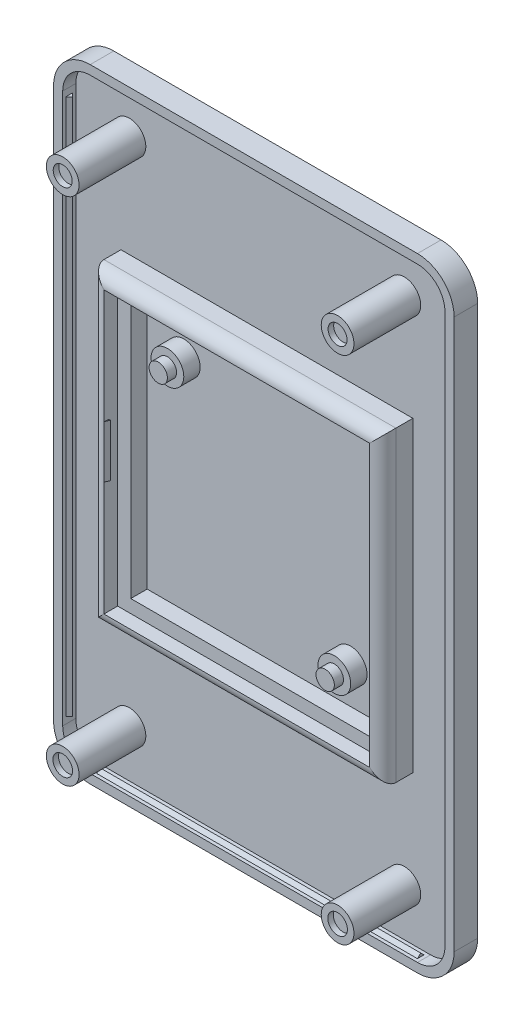
SolidWorks part; units mm, degrees
ref_plane "Front Plane" through (0, 0, 0) normal (0, 0, 1) x (1, 0, 0)
ref_plane "Top Plane" through (0, 0, 0) normal (0, 1, 0) x (1, 0, 0)
ref_plane "Right Plane" through (0, 0, 0) normal (1, 0, 0) x (0, 0, -1)
sketch "Esquisse2" plane through (0, 0, 0) normal (0, 0, 1) x (1, 0, 0)
  line L1 (-29.2, -46.2) -> (29.2, -46.2)
  line L2 (-29.2, -46.2) -> (-29.2, 46.2)
  line L3 (-29.2, 46.2) -> (29.2, 46.2)
  line L4 (29.2, -46.2) -> (29.2, 46.2)
  line L5 (-29.2, -46.2) -> (29.2, 46.2) construction
  line L6 (-29.2, 46.2) -> (29.2, -46.2) construction
  point P0 (0, 0)
  dimension "D1" = 92.4
  dimension "D2" = 58.4
extrude "Boss.-Extru.1" add sketch "Esquisse2" against normal blind 1.6
fillet "Congé1" radius 4.2 4 edges at (-29.2, 46.2, -0.8) (29.2, 46.2, -0.8) (29.2, -46.2, -0.8) (-29.2, -46.2, -0.8)
sketch "Esquisse3" plane through (0, 0, 0) normal (0, 0, 1) x (1, 0, 0)
  line L1 (20.3, -21.45) -> (-20.3, -21.45)
  line L2 (20.3, -21.45) -> (20.3, 21.45)
  line L3 (20.3, 21.45) -> (-20.3, 21.45)
  line L4 (-20.3, -21.45) -> (-20.3, 21.45)
  line L5 (20.3, -21.45) -> (-20.3, 21.45) construction
  line L6 (20.3, 21.45) -> (-20.3, -21.45) construction
  point P0 (0, 0)
  dimension "D1" = 42.9
  dimension "D2" = 40.6
extrude "Extru.-Mince1" add sketch "Esquisse3" along normal blind 2.5 thin contours L4 L3 L2 L1 thin type one direction reverse wall 2
sketch "Esquisse4" plane through (0, 0, 0) normal (0, 0, 1) x (1, 0, 0)
  line L0 (20.3, 21.45) -> (-20.3, 21.45) construction
  line L1 (-12.7, 13.95) -> (-20.2, 13.95)
  line L2 (-12.7, 13.95) -> (-12.7, 21.45)
  line L3 (-12.7, 21.45) -> (-20.2, 21.45)
  line L4 (-20.2, 13.95) -> (-20.2, 21.45)
  line L5 (-12.7, 13.95) -> (-20.2, 21.45) construction
  line L6 (-12.7, 21.45) -> (-20.2, 13.95) construction
  circle A0 centre (-12.7, 13.95) radius 2.5
  point P0 (-16.45, 17.7)
  dimension "D1" = 7.5
  dimension "D2" = 7.5
extrude "Boss.-Extru.2" add sketch "Esquisse4" along normal blind 2.5 contours A0
sketch "Esquisse5" plane through (0, 0, 0) normal (0, 0, 1) x (1, 0, 0)
  circle A0 centre (-12.7, 13.95) radius 1.4
extrude "Boss.-Extru.3" add sketch "Esquisse5" along normal blind 3.9
sketch "Esquisse6" plane through (0, 0, 0) normal (0, 0, 1) x (1, 0, 0)
  line L1 (20.3, -21.45) -> (12.8, -21.45) construction
  line L2 (20.3, -21.45) -> (20.3, -13.95) construction
  line L3 (20.3, -13.95) -> (12.8, -13.95) construction
  line L4 (12.8, -21.45) -> (12.8, -13.95)
  circle A0 centre (12.8, -13.95) radius 2.5
  dimension "D1" = 7.5
  dimension "D2" = 7.5
extrude "Boss.-Extru.4" add sketch "Esquisse6" along normal blind 2.5 contours A0
sketch "Esquisse7" plane through (0, 0, 0) normal (0, 0, 1) x (1, 0, 0)
  circle A0 centre (12.8, -13.95) radius 1.4
extrude "Boss.-Extru.5" add sketch "Esquisse7" along normal blind 3.9 contours A0
sketch "Esquisse8" plane through (0, 0, 0) normal (0, 0, 1) x (1, 0, 0)
  line L1 (20.3, -21.45) -> (-20.3, -21.45)
  line L2 (20.3, -21.45) -> (20.3, 21.45)
  line L3 (20.3, 21.45) -> (-20.3, 21.45)
  line L4 (-20.3, -21.45) -> (-20.3, 21.45)
extrude "Extru.-Mince2" add sketch "Esquisse8" along normal blind 4.6 thin thin type one direction wall 2
fillet "Congé2" radius 2 4 edges at (22.3, 0, 4.6) (0, 23.45, 4.6) (-22.3, 0, 4.6) (0, -23.45, 4.6)
sketch "Esquisse10" plane through (0, 0, 0) normal (0, 0, 1) x (1, 0, 0)
  line L1 (21, -39) -> (-21, -39)
  line L2 (21, -39) -> (21, 39)
  line L3 (21, 39) -> (-21, 39)
  line L4 (-21, -39) -> (-21, 39)
  line L5 (21, -39) -> (-21, 39) construction
  line L6 (21, 39) -> (-21, -39) construction
  circle A0 centre (21, -39) radius 2.5
  circle A1 centre (-21, -39) radius 2.5
  circle A2 centre (-21, 39) radius 2.5
  circle A3 centre (21, 39) radius 2.5
  point P0 (0, 0)
  dimension "D1" = 78
  dimension "D2" = 42
extrude "Boss.-Extru.6" add sketch "Esquisse10" along normal blind 10.2 contours A1 | A0 | A3 | A2
sketch "Esquisse13" plane through (0, 0, 10.2) normal (0, 0, 1) x (1, 0, 0)
  circle A0 centre (21, -39) radius 1.5
  circle A1 centre (-21, -39) radius 1.5
  circle A2 centre (-21, 39) radius 1.45
  circle A3 centre (21, 39) radius 1.45
extrude "Enlèv. mat.-Extru.1" cut sketch "Esquisse13" against normal blind 0.85
sketch "Esquisse14" plane through (0, 0, 0) normal (0, 0, 1) x (1, 0, 0)
  line L0 (25, 46.2) -> (-25, 46.2) construction
  line L1 (29.2, -42) -> (29.2, 42) construction
  line L2 (-29.2, 42) -> (-29.2, -42) construction
  line L3 (-25, -46.2) -> (25, -46.2) construction
  line L4 (25, 46.2) -> (-25, 46.2)
  line L5 (29.2, -42) -> (29.2, 42)
  line L6 (-29.2, 42) -> (-29.2, -42)
  line L7 (-25, -46.2) -> (25, -46.2)
  arc A0 (-25, 46.2) -> (-29.2, 42) centre (-25, 42) ccw construction
  arc A1 (29.2, 42) -> (25, 46.2) centre (25, 42) ccw construction
  arc A2 (25, -46.2) -> (29.2, -42) centre (25, -42) ccw construction
  arc A3 (-29.2, -42) -> (-25, -46.2) centre (-25, -42) ccw construction
  arc A4 (-25, 46.2) -> (-29.2, 42) centre (-25, 42) ccw
  arc A5 (29.2, 42) -> (25, 46.2) centre (25, 42) ccw
  arc A6 (25, -46.2) -> (29.2, -42) centre (25, -42) ccw
  arc A7 (-29.2, -42) -> (-25, -46.2) centre (-25, -42) ccw
extrude "Extru.-Mince3" add sketch "Esquisse14" along normal blind 2 and the other way blind 1.6 thin thin type one direction wall 1.4
sketch3d "Esquisse3D7"
  line L0 (20.3, -21.45, 4.6) -> (20.3, 0, 4.6) construction
  line L1 (20.3, -21.45, 4.6) -> (20.3, 21.45, 4.6) construction
  line L2 (20.3, 0, 4.6) -> (20.3, 0, 3.9)
  line L3 (20.3, 0, 4.6) -> (20.05, 0, 3.9)
  line L4 (20.05, 0, 3.9) -> (20.3, 0, 3.9)
extrude "Boss.-Extru.9" add sketch "Esquisse3D7" along direction (0, 1, 0) on the side of the normal blind 4 and the other way blind 4 contours L3 L4 L2
sketch3d "Esquisse3D8"
  line L0 (-20.3, 0, 4.6) -> (-20.0062, 0, 3.9153)
  line L1 (-20.3, 21.45, 4.6) -> (-20.3, -21.45, 4.6) construction
  line L2 (-20.0062, 0, 3.9153) -> (-20.2371, 0, 3.8947)
  line L3 (-20.2371, 0, 3.8947) -> (-20.3, 0, 4.6)
extrude "Boss.-Extru.10" add sketch "Esquisse3D8" along direction (0, -1, 0) on the side of the normal blind 4 and the other way blind 4 separate body
sketch "Esquisse16" plane through (29.2, 0, 0) normal (-1, 0, 0) x (0, 0, 1)
  line L0 (2, 0) -> (0, 0)
  line L1 (2, -42) -> (2, 42) construction
  line L2 (0, -42) -> (0, 42) construction
sketch3d "Esquisse3D9"
  line L2 (29.2, 0, 1) -> (29.2, 0, 1.5111)
  line L3 (29.2, 0, 2) -> (29.2, 0, 0) construction
  line L4 (29.2, 0, 1) -> (29.2, 0, 0.4889)
  line L6 (20.3, -21.45, 4.6) -> (20.3, -4, 4.6) construction
  line L7 (29.2, 0, 1.5111) -> (28.6889, 0, 1)
  line L8 (28.6889, 0, 1) -> (29.2, 0, 0.4889)
extrude "Boss.-Extru.11" add sketch "Esquisse3D9" along direction (0, 1, 0) on the side of the normal blind 41 and the other way blind 41
mirror "Symétrie1" about plane through (0, 0, 0) normal (1, 0, 0) of "Boss.-Extru.11"
sketch "Esquisse19" plane through (0, 46.2, 0) normal (0, -1, 0) x (-1, 0, 0)
  line L0 (0, -2) -> (0, 0) construction
  line L1 (-25, -2) -> (25, -2) construction
  line L2 (-25, 0) -> (25, 0) construction
  line L3 (0, -1) -> (0, -1.5)
  line L4 (0, -1) -> (0, -0.5)
sketch3d "Esquisse3D12"
  line L2 (0, 46.2, 1.5) -> (0, 45.7, 1)
  line L3 (0, 45.7, 1) -> (0, 46.2, 0.5)
  line L5 (0, 46.2, 1.5) -> (0, 46.2, 0.5)
  point P3 (0, 0, 0)
  dimension "D1" = 90
extrude "Boss.-Extru.12" add sketch "Esquisse3D12" along direction (-1, 0, 0) on the side of the normal blind 24.5 and the other way blind 24.5
mirror "Symétrie2" about plane through (0, 0, 0) normal (0, 1, 0) of "Boss.-Extru.12"
sketch "Esquisse31" plane through (0, 0, -1.6) normal (0, 0, -1) x (-1, 0, 0)
  spline S0 degree 3 poles (4.3492, -9.9887) (3.9683, -9.8345) (3.6961, -9.4898) (3.6327, -9.0816) knots 0 0 0 0 1 1 1 1
  spline S1 degree 3 poles (3.6327, -9.0816) (3.5873, -8.8458) (3.6327, -8.6825) (3.9955, -8.0295) knots 1 1 1 1 2 2 2 2
  spline S2 degree 3 poles (3.9955, -8.0295) (5.356, -5.5805) (6.0544, -2.8141) (6.0181, -0.0113) knots 2 2 2 2 3 3 3 3
  spline S3 degree 3 poles (6.0181, -0.0113) (6.0544, 2.7098) (5.3923, 5.3673) (4.0862, 7.7528) knots 3 3 3 3 4 4 4 4
  spline S4 degree 3 poles (4.0862, 7.7528) (3.8957, 8.1519) (3.7234, 8.5329) (3.5782, 8.941) knots 4 4 4 4 5 5 5 5
  spline S5 degree 3 poles (3.5782, 8.941) (3.6327, 9.2857) (3.805, 9.6032) (4.0862, 9.7937) knots 5 5 5 5 6 6 6 6
  spline S6 degree 3 poles (4.0862, 9.7937) (4.4943, 10.0113) (4.9932, 9.966) (5.3651, 9.712) knots 6 6 6 6 7 7 7 7
  spline S7 degree 3 poles (5.3651, 9.712) (5.619, 9.3855) (5.8367, 9.059) (6.0181, 8.678) knots 7 7 7 7 8 8 8 8
  spline S8 degree 3 poles (6.0181, 8.678) (6.9977, 6.7914) (7.6599, 4.7959) (7.9864, 2.7098) knots 8 8 8 8 9 9 9 9
  spline S9 degree 3 poles (7.9864, 2.7098) (8.195, 1.068) (8.2222, -0.6009) (8.068, -2.2517) knots 9 9 9 9 10 10 10 10
  spline S10 degree 3 poles (8.068, -2.2517) (7.7868, -4.3741) (7.161, -6.424) (6.1995, -8.3379) knots 10 10 10 10 11 11 11 11
  spline S11 degree 3 poles (6.1995, -8.3379) (5.619, -9.4989) (5.2925, -9.9887) (4.9478, -9.9887) knots 11 11 11 11 12 12 12 12
  spline S12 degree 3 poles (4.9478, -9.9887) (4.8753, -9.9887) (4.7937, -9.9887) (4.7211, -9.9887) knots 12 12 12 12 13 13 13 13
  spline S13 degree 3 poles (4.7211, -9.9887) (4.5941, -9.9887) (4.4762, -9.9887) (4.3492, -9.9887) knots 13 13 13 13 14 14 14 14
  spline S14 degree 3 poles (0.3946, -7.9388) (0.3946, -7.9539) (0.3946, -7.969) (0.3946, -7.9841) knots 9 9 9 9 10 10 10 10
  spline S15 degree 3 poles (2.4444, -5.907) (1.6825, -7.6213) (1.1474, -8.1746) (0.3946, -7.9388) knots 8 8 8 8 9 9 9 9
  spline S16 degree 3 poles (2.9524, 4.5782) (4.1134, 1.1406) (3.932, -2.6054) (2.4444, -5.907) knots 7 7 7 7 8 8 8 8
  spline S17 degree 3 poles (1.4014, 7.6984) (2.0544, 6.737) (2.5714, 5.6848) (2.9524, 4.5782) knots 6 6 6 6 7 7 7 7
  spline S18 degree 3 poles (-0.1497, 7.5714) (0.2494, 8.0159) (0.9116, 8.0794) (1.4014, 7.6984) knots 5 5 5 5 6 6 6 6
  spline S19 degree 3 poles (0.1224, 5.7574) (-0.449, 6.9002) (-0.4853, 7.0816) (-0.1497, 7.5714) knots 4 4 4 4 5 5 5 5
  spline S20 degree 3 poles (1.5193, 1.0227) (1.3923, 2.6825) (0.9116, 4.2971) (0.1224, 5.7574) knots 3 3 3 3 4 4 4 4
  spline S21 degree 3 poles (0.195, -5.6712) (1.2653, -3.6122) (1.7279, -1.2902) (1.5193, 1.0227) knots 2 2 2 2 3 3 3 3
  spline S22 degree 3 poles (-0.3401, -6.7868) (-0.3401, -6.678) (-0.059, -6.1791) (0.195, -5.6712) knots 1 1 1 1 2 2 2 2
  spline S23 degree 3 poles (0.3946, -7.9841) (-0.1224, -7.839) (-0.449, -7.3129) (-0.3401, -6.7868) knots 0 0 0 0 1 1 1 1
  spline S24 degree 3 poles (-3.6871, -5.907) (-3.6871, -5.9252) (-3.6871, -5.9433) (-3.6871, -5.9615) knots 10 10 10 10 11 11 11 11
  spline S25 degree 3 poles (-3.1701, -5.9887) (-3.3424, -6.0068) (-3.5238, -5.9887) (-3.6871, -5.907) knots 9 9 9 9 10 10 10 10
  spline S26 degree 3 poles (-1.9456, -4.7279) (-2.4354, -5.6803) (-2.6803, -5.907) (-3.1701, -5.9887) knots 8 8 8 8 9 9 9 9
  spline S27 degree 3 poles (-0.7937, -0.0113) (-0.7574, -1.6531) (-1.1565, -3.2857) (-1.9456, -4.7279) knots 7 7 7 7 8 8 8 8
  spline S28 degree 3 poles (-1.9546, 4.6054) (-1.1837, 3.1905) (-0.7846, 1.6032) (-0.7937, -0.0113) knots 6 6 6 6 7 7 7 7
  spline S29 degree 3 poles (-3.3515, 5.9116) (-2.771, 5.9116) (-2.4444, 5.6304) (-1.9546, 4.6054) knots 5 5 5 5 6 6 6 6
  spline S30 degree 3 poles (-4.0499, 5.6485) (-3.8776, 5.8481) (-3.6236, 5.9478) (-3.3515, 5.9116) knots 4 4 4 4 5 5 5 5
  spline S31 degree 3 poles (-3.941, 3.8345) (-4.5306, 4.9773) (-4.5306, 5.2132) (-4.0499, 5.6485) knots 3 3 3 3 4 4 4 4
  spline S32 degree 3 poles (-3.941, -4.0385) (-2.5896, -1.5896) (-2.5896, 1.3855) (-3.941, 3.8345) knots 2 2 2 2 3 3 3 3
  spline S33 degree 3 poles (-4.3492, -5.1814) (-4.3492, -5) (-4.3492, -4.7642) (-3.941, -4.0385) knots 1 1 1 1 2 2 2 2
  spline S34 degree 3 poles (-3.6871, -5.9615) (-4.0136, -5.8163) (-4.2585, -5.5261) (-4.3492, -5.1814) knots 0 0 0 0 1 1 1 1
  spline S35 degree 3 poles (-7.4966, -4.0295) (-7.4996, -4.0295) (-7.5026, -4.0295) (-7.5057, -4.0295) knots 9 9 9 9 10 10 10 10
  spline S36 degree 3 poles (-5.9637, -3.3039) (-6.4263, -4.0023) (-6.9524, -4.2109) (-7.4966, -4.0295) knots 8 8 8 8 9 9 9 9
  spline S37 degree 3 poles (-5.9637, 3.2902) (-4.6485, 1.2857) (-4.6485, -1.2993) (-5.9637, -3.3039) knots 7 7 7 7 8 8 8 8
  spline S38 degree 3 poles (-7.2517, 4.0975) (-6.7619, 4.1882) (-6.4172, 3.9796) (-5.9637, 3.2902) knots 6 6 6 6 7 7 7 7
  spline S39 degree 3 poles (-8.1587, 2.873) (-8.2585, 3.4444) (-7.8776, 3.9887) (-7.2517, 4.0975) knots 5 5 5 5 6 6 6 6
  spline S40 degree 3 poles (-7.7596, 2.1565) (-7.9138, 2.3832) (-8.0408, 2.6281) (-8.1587, 2.873) knots 4 4 4 4 5 5 5 5
  spline S41 degree 3 poles (-7.1701, -0.0113) (-7.1066, 0.7596) (-7.3152, 1.5215) (-7.7596, 2.1565) knots 3 3 3 3 4 4 4 4
  spline S42 degree 3 poles (-7.7959, -2.1519) (-7.3424, -1.5351) (-7.1247, -0.7732) (-7.1701, -0.0113) knots 2 2 2 2 3 3 3 3
  spline S43 degree 3 poles (-8.1587, -3.322) (-8.2494, -3.0045) (-8.1587, -2.7324) (-7.7959, -2.1519) knots 1 1 1 1 2 2 2 2
  spline S44 degree 3 poles (-7.5057, -4.0295) (-7.805, -3.8844) (-8.0408, -3.6395) (-8.1587, -3.322) knots 0 0 0 0 1 1 1 1
extrude "Enlèv. mat.-Extru.4" cut sketch "Esquisse31" against normal blind 0.4
